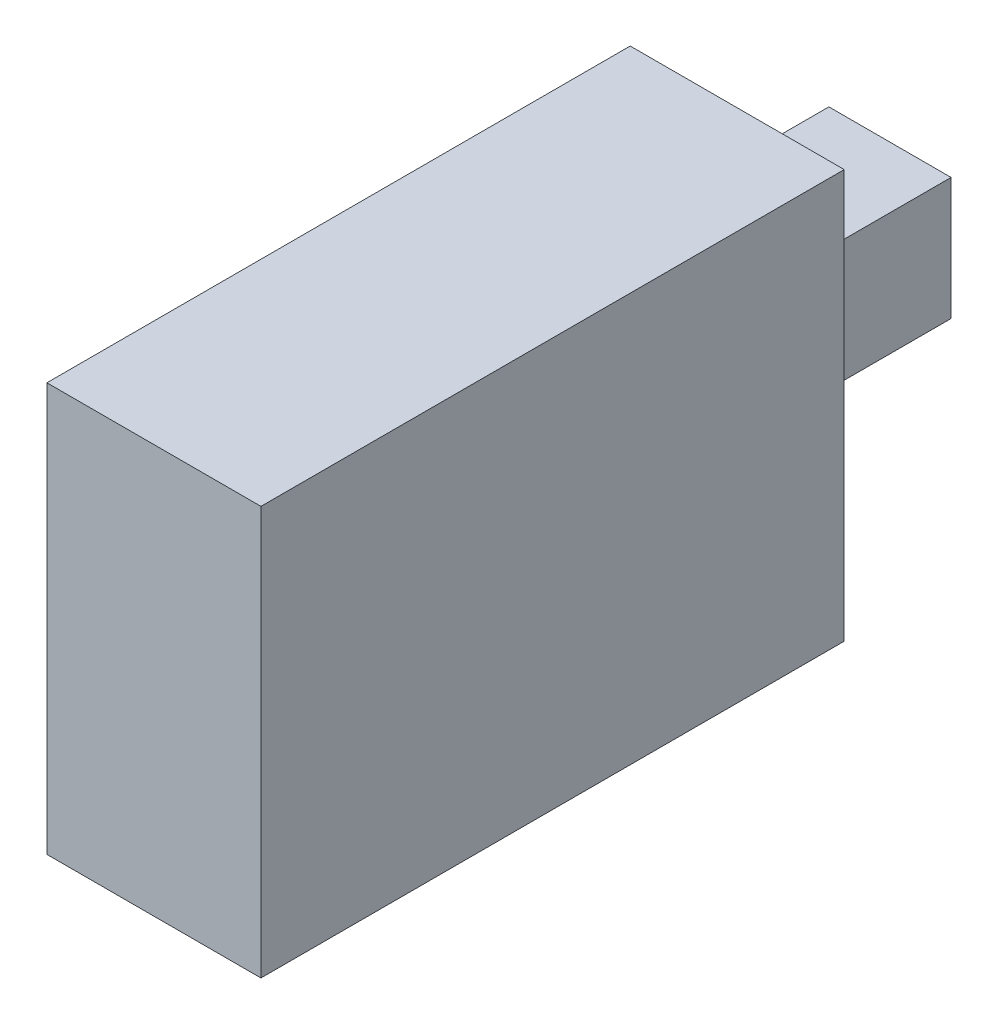
SolidWorks part; units mm, degrees
material "ABS PC"
ref_plane "Front Plane" through (0, 0, 0) normal (0, 0, 1) x (1, 0, 0)
ref_plane "Top Plane" through (0, 0, 0) normal (0, 1, 0) x (1, 0, 0)
ref_plane "Right Plane" through (0, 0, 0) normal (1, 0, 0) x (0, 0, -1)
sketch "Sketch1" plane through (0, 0, 0) normal (0, 0, 1) x (1, 0, 0)
  line L0 (-3.3274, -6.35) -> (3.3274, -6.35)
  line L1 (3.3274, 6.35) -> (3.3274, -6.35)
  line L2 (-3.3274, 6.35) -> (3.3274, 6.35)
  line L3 (-3.3274, 6.35) -> (-3.3274, -6.35)
  line L4 (0, 6.35) -> (0, -6.35) construction
  dimension "D1" = 6.6548
  dimension "D2" = 12.7
extrude "Extrude1" add sketch "Sketch1" along normal mid plane 18.136
sketch "Sketch2" plane through (0, 0, -9.068) normal (0, 0, -1) x (-1, 0, 0)
  line L0 (1.9, 3.05) -> (1.9, -0.75)
  line L1 (1.9, -0.75) -> (-1.9, -0.75)
  line L2 (-1.9, -0.75) -> (-1.9, 3.05)
  line L3 (-1.9, 3.05) -> (1.9, 3.05)
  line L4 (0, -0.75) -> (0, 3.05) construction
  line L5 (-3.3274, 6.35) -> (3.3274, 6.35) construction
  dimension "D1" = 3.8
  dimension "D2" = 3.3
extrude "Extrude2" add sketch "Sketch2" along normal blind 4.75
